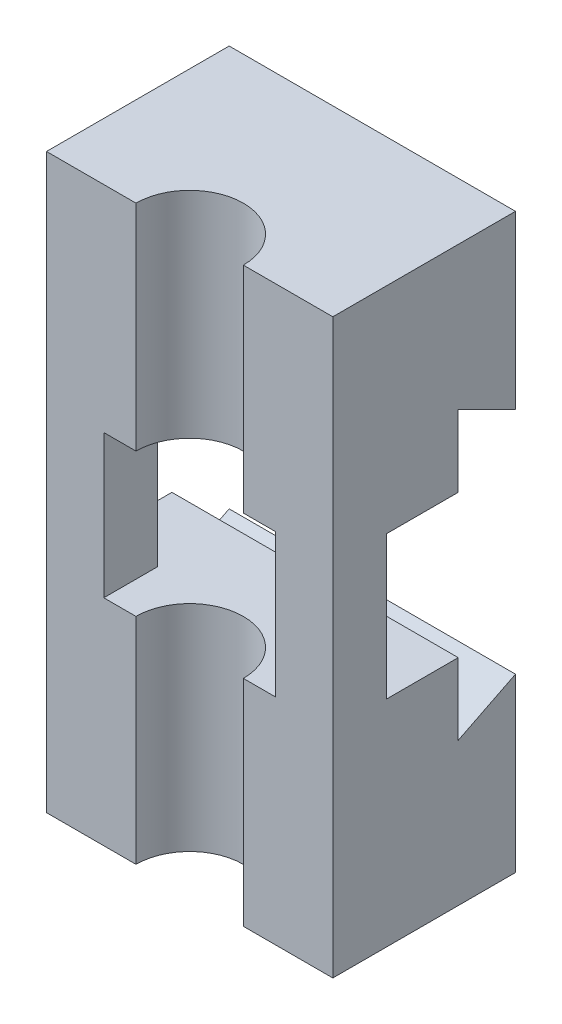
SolidWorks part; units mm, degrees
ref_plane "Front Plane" through (0, 0, 0) normal (1, 0, 0) x (0, 1, 0)
ref_plane "Top Plane" through (0, 0, 0) normal (0, 0, 1) x (0, 1, 0)
ref_plane "Right Plane" through (0, 0, 0) normal (0, 1, 0) x (-1, 0, 0)
sketch "Sketch2" plane through (0, 0, 0) normal (1, 0, 0) x (0, 1, 0)
  line L0 (0, -7.5) -> (-4, -7.5)
  line L1 (-10, -7.5) -> (10, -7.5)
  line L2 (-10, -7.5) -> (-10, 7.5)
  line L3 (-10, 7.5) -> (10, 7.5)
  line L4 (10, -7.5) -> (10, 7.5)
  line L5 (-10, -7.5) -> (10, 7.5) construction
  line L6 (-10, 7.5) -> (10, -7.5) construction
  line L11 (-5, -9.5) -> (5, -5.5) construction
  line L12 (-5, -5.5) -> (5, -9.5) construction
  line L13 (-4, -7.5) -> (-5, -5.5)
  line L14 (0, -7.5) -> (4, -7.5)
  line L15 (4, -7.5) -> (5, -5.5)
  line L16 (-5, -5.5) -> (5, -5.5)
  line L22 (-2.5, -3) -> (2.5, -3)
  line L23 (-2.5, -3) -> (-2.5, -5.5)
  line L24 (-2.5, -5.5) -> (2.5, -5.5)
  line L25 (2.5, -3) -> (2.5, -5.5)
  point P0 (0, 0)
  point P6 (0, -7.5)
  dimension "D1" = 20
  dimension "D2" = 15
  dimension "D3" = 10
  dimension "D4" = 4
  dimension "D6" = 2.5
  dimension "D7" = 5
extrude "Boss-Extrude1" add sketch "Sketch2" along normal blind 10 contours L22 L25 L16 L15 L1 L4 L3 L2 L13 L23 region at (0, 0, 0.6288)
sketch "Sketch4" plane through (0, 0, -3) normal (0, 0, -1) x (1, 0, 0)
  line L0 (5, 2.5) -> (2, 2.5)
  line L1 (10, 2.5) -> (0, 2.5) construction
  line L2 (2, 2.5) -> (2, -2.5)
  line L3 (10, -2.5) -> (0, -2.5) construction
  line L4 (2, -2.5) -> (8, -2.5)
  line L5 (8, -2.5) -> (8, 2.5)
  line L6 (8, 2.5) -> (5, 2.5)
extrude "Cut-Extrude2" cut sketch "Sketch4" against normal blind 4.88
sketch "Sketch6" plane through (0, 2.5, 0) normal (0, -1, 0) x (1, 0, 0)
  line L1 (2, 1.88) -> (8, 1.88)
  line L2 (2, 1.88) -> (2, -4.12)
  line L3 (2, -4.12) -> (8, -4.12)
  line L4 (8, 1.88) -> (8, -4.12)
  circle A0 centre (5, -1.12) radius 1.875
  dimension "D1" = 6
extrude "Cut-Extrude3" [suppressed] cut sketch "Sketch6" along normal through all both and the other way through all draft 1 contours A0
extrude "Cut-Extrude4" cut sketch "Sketch6<3>" against normal through all both and the other way through all contours A0 region at (5, 2.5, -1.12)
sketch "Sketch6<3>" plane through (0, 2.5, 0) normal (0, -1, 0) x (1, 0, 0) same geometry as "Sketch6"
sketch "Sketch7" plane through (0, 10, 0) normal (0, 1, 0) x (-1, 0, 0)
  line L0 (0, -7.5) -> (0, 7.5) construction
  line L1 (-10, -7.5) -> (0, -7.5)
  line L2 (-10, -7.5) -> (-10, -1.12)
  line L3 (-10, -1.12) -> (0, -1.12)
  line L4 (0, -7.5) -> (0, -1.12)
extrude "Cut-Extrude5" cut sketch "Sketch7" against normal through all both and the other way through all flip side to cut
